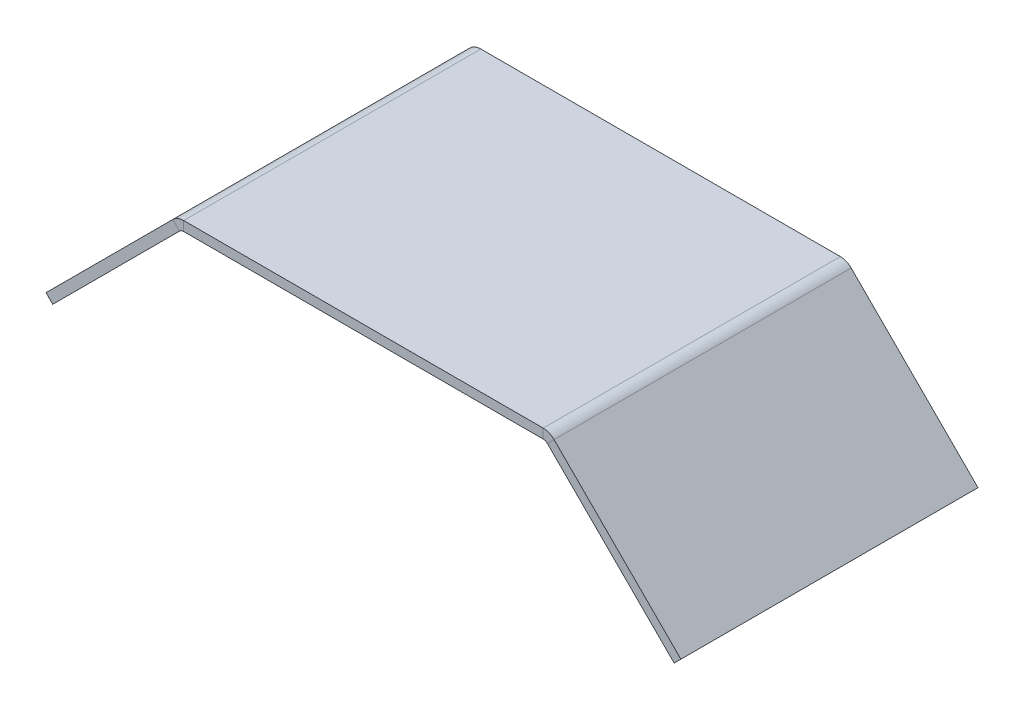
SolidWorks part; units mm, degrees
note: The reader was unsure of these and kept them because the rebuilt part matched: thickness of "Base-Flange2", "Edge-Flange1", "Sheet-Metal2", "Sheet-Metal3"; flange length of "Edge-Flange1".
ref_plane "Front Plane" through (0, 0, 0) normal (0, 0, 1) x (1, 0, 0)
ref_plane "Top Plane" through (0, 0, 0) normal (0, 1, 0) x (1, 0, 0)
ref_plane "Right Plane" through (0, 0, 0) normal (1, 0, 0) x (0, 0, -1)
sketch "Sketch7" plane through (0, 0, 0) normal (0, 1, 0) x (1, 0, 0)
  line L1 (-30.734, -25.4) -> (30.734, -25.4)
  line L2 (-30.734, -25.4) -> (-30.734, 25.4)
  line L3 (-30.734, 25.4) -> (30.734, 25.4)
  line L4 (30.734, -25.4) -> (30.734, 25.4)
  line L5 (-30.734, -25.4) -> (30.734, 25.4) construction
  line L6 (-30.734, 25.4) -> (30.734, -25.4) construction
  point P0 (0, 0)
  dimension "D1" = 25.4
  dimension "D2" = 61.468
base flange "Base-Flange2" sketch "Sketch7" thickness 1.6256 reverse thickness direction no parameters "D1"=1
edge flange "Edge-Flange1" sketch "Sketch16" flange profiles "Sketch16", "Sketch17" flange angle 135 flange length 31.75 flange position bend outside bend radius 1 thickness 1.6256 relief rectangular parameters "D6"=10, "D8"=1
sketch "Sketch16" plane through (-30.734, -1.6256, 0) normal (-0.7071, 0.7071, 0) x (0, 0, -1)
  line L2 (25.4, 0) -> (25.4, 31.0767)
  line L3 (25.4, 31.0767) -> (-25.4, 31.0767)
  line L4 (-25.4, 31.0767) -> (-25.4, 0)
  line L53 (25.4, 0) -> (-25.4, 0) construction
  line L54 (25.4, 0) -> (-25.4, 0)
sketch "Sketch17" plane through (30.734, -1.6256, 0) normal (0.7071, 0.7071, 0) x (0, 0, 1)
  line L2 (25.4, 0) -> (25.4, 31.0767)
  line L3 (25.4, 31.0767) -> (-25.4, 31.0767)
  line L4 (-25.4, 31.0767) -> (-25.4, 0)
  line L21 (25.4, 0) -> (-25.4, 0) construction
  line L22 (25.4, 0) -> (-25.4, 0)
bend "EdgeBend1" bend radius 1 bend angle 45 parameters "D5"=1
bend "EdgeBend2" bend radius 1 bend angle 45 parameters "D5"=2
sketch "Sketch18" plane through (0, 0, 0) normal (0, 0, 1) x (1, 0, 0)
  line L0 (-30.734, -1.6256) -> (30.734, -1.6256) construction
  circle A0 centre (0, -77.8256) radius 76.2 construction
  dimension "D1" = 152.4
sketch "Bend-Lines1" [suppressed]
sketch "Bounding-Box1" [suppressed]
sheet metal parameters "Sheet-Metal2" thickness 1.6256 parameters "D1"=1
flat pattern "Flat-Pattern2" [suppressed]
sketch "Bend-Lines3" plane through (0, 0, 0) normal (0, 1, 0) x (1, 0, 0)
sketch3d "Bounding-Box3" [suppressed]
  line L0 (-30.734, 25.4, 0) -> (30.734, 25.4, 0) construction
  line L1 (-30.734, -25.4, 0) -> (30.734, -25.4, 0) construction
  line L2 (-30.734, 25.4, 0) -> (-30.734, -25.4, 0) construction
  line L3 (30.734, 25.4, 0) -> (30.734, -25.4, 0) construction
sheet metal parameters "Sheet-Metal3" thickness 1.6256 parameters "D1"=1
flat pattern "Flat-Pattern2"
sketch "Bend-Lines3" plane through (0, 0, 0) normal (0, 1, 0) x (1, 0, 0)
  line L0 (31.4459, -25.4) -> (31.4459, 25.4) construction
  line L1 (-31.4459, 25.4) -> (-31.4459, -25.4) construction
  line L2 (31.4459, -25.4) -> (31.4459, 25.4) construction
  line L3 (-31.4459, 25.4) -> (-31.4459, -25.4) construction
sketch3d "Bounding-Box3" [suppressed]
  line L0 (62.8202, 25.4, 0) -> (-62.8202, 25.4, 0) construction
  line L1 (62.8202, -25.4, 0) -> (-62.8202, -25.4, 0) construction
  line L2 (62.8202, 25.4, 0) -> (62.8202, -25.4, 0) construction
  line L3 (-62.8202, 25.4, 0) -> (-62.8202, -25.4, 0) construction
bend of the flat pattern "Flatten-<EdgeBend1>1"
bend of the flat pattern "Flatten-<EdgeBend2>1"
